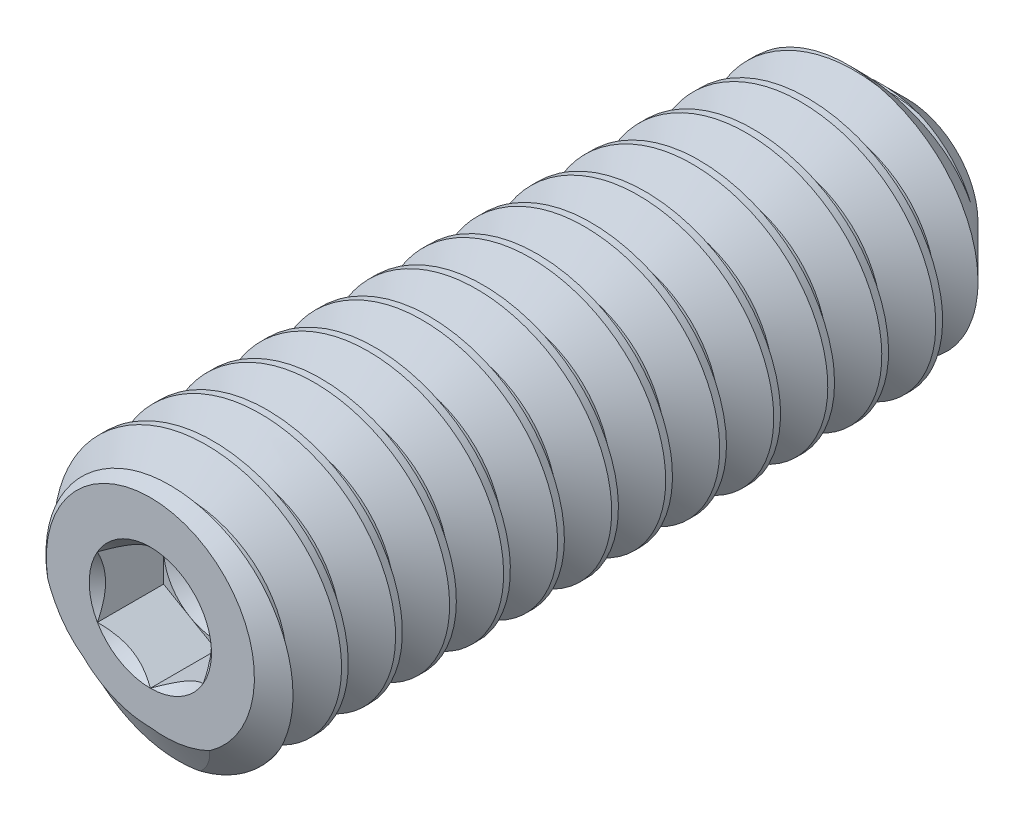
SolidWorks part; units mm, degrees
ref_plane "Front" through (0, 0, 0) normal (0, 0, 1) x (1, 0, 0)
ref_plane "Top" through (0, 0, 0) normal (0, 1, 0) x (1, 0, 0)
ref_plane "Right" through (0, 0, 0) normal (1, 0, 0) x (0, 0, -1)
sketch "Sketch22" plane through (0, 0, 0) normal (1, 0, 0) x (0, 0, -1)
  line L0 (-2.9952, 0) -> (-2.9952, 0.8738)
  line L1 (-2.9952, 0.8738) -> (-2.8422, 1.0922)
  line L2 (-2.8422, 1.0922) -> (2.8611, 1.0922)
  line L3 (2.8611, 1.0922) -> (3.3548, 0.5985)
  line L4 (3.3548, 0.5985) -> (2.9952, 0)
  line L5 (2.9952, 0) -> (-2.9952, 0)
  line L6 (2.9952, 0) -> (3.3548, 0) construction
  line L7 (3.3548, 0) -> (3.3548, 0.5985) construction
  line L8 (3.3548, -0.5985) -> (2.9952, 0) construction
  line L9 (-2.8422, -1.0922) -> (2.8611, -1.0922) construction
  line L10 (3.3548, -1.0922) -> (3.3548, 1.0922) construction
  line L11 (3.3548, 1.0922) -> (2.9012, 1.0922) construction
  point P11 (2.2209, -1.0922)
  point P15 (3.3548, 0)
  dimension "D3" = 35
  dimension "D5" = 118
  dimension "D6" = 45
  dimension "D7" = 1.7475
  dimension "D1" = 1.1339
revolve "Revolve1" add sketch "Sketch22" angle 360 about L6
ref_plane "Plane1" through (0, 0, -3.3548) normal (0, 0, 1) x (1, 0, 0)
sketch "Sketch27" plane through (0, 0, -3.3548) normal (0, 0, 1) x (1, 0, 0)
  circle A0 centre (0, 0) radius 1.0922 construction
  circle A1 centre (0, 0) radius 1.0922
sketch "Sketch23" plane through (0, 0, 2.9952) normal (0, 0, 1) x (1, 0, 0)
  line L1 (0, 0.5133) -> (-0.4445, 0.2566)
  line L2 (-0.4445, 0.2566) -> (-0.4445, -0.2566)
  line L3 (-0.4445, -0.2566) -> (0, -0.5133)
  line L4 (0, -0.5133) -> (0.4445, -0.2566)
  line L5 (0.4445, -0.2566) -> (0.4445, 0.2566)
  line L6 (0.4445, 0.2566) -> (0, 0.5133)
  circle A0 centre (0, 0) radius 0.4445 construction
extrude "Cut-Extrude10" cut sketch "Sketch23" against normal blind 0.5556
sketch "Sketch24" plane through (0, 0, 2.9952) normal (0, 0, 1) x (1, 0, 0)
  circle A0 centre (0, 0) radius 0.5133
extrude "Cut-Extrude11" cut sketch "Sketch24" against normal through all draft 45
sketch "Sketch26" plane through (0, 0, 2.4396) normal (0, 0, 1) x (1, 0, 0)
  circle A0 centre (0, 0) radius 0.4445 construction
  circle A1 centre (0, 0) radius 0.4445
extrude "Cut-Extrude12" cut sketch "Sketch26" against normal through all draft 60
sketch "Sketch31" plane through (0, 0, 0) normal (1, 0, 0) x (0, 0, -1)
  line L2 (2.9952, 0) -> (3.3548, -0.5985)
  line L3 (3.3548, 0.5985) -> (2.9952, 0)
ref_axis "Center Axis1" through (0, 0, -42.9554) along (0, 0, 1)
ref_plane "Contact Plane1" through (0, 0, -3.3548) normal (0, 0, 1) x (1, 0, 0)
ref_plane "Contact Plane2" through (0, 0, 2.9952) normal (0, 0, 1) x (1, 0, 0)
curve "Helix/Spiral1" pitch 0.4536 height 6.8036 radius 1.0922 centre (0, 0, -3.3548) axis (0, 0, 1) start towards (0, 1, 0)
sketch "Sketch32" plane through (0, 0, 0) normal (1, 0, 0) x (0, 0, -1)
  line L0 (3.3265, 1.1413) -> (3.78, 1.1413) construction
  line L1 (3.78, 1.1413) -> (3.5532, 0.7485) construction
  line L2 (3.5532, 0.7485) -> (3.3265, 1.1413) construction
  line L3 (3.3548, 1.0922) -> (2.9012, 1.0922) construction
  line L4 (3.5532, 0.7485) -> (3.5532, 0.7976) construction
  line L5 (3.5532, 1.1413) -> (3.5532, 1.0922) construction
  line L6 (3.5249, 0.7976) -> (3.5816, 0.7976)
  line L7 (3.3548, 1.0922) -> (3.7517, 1.0922) construction
  line L8 (3.3406, 1.1168) -> (3.7659, 1.1168)
  line L9 (3.3406, 1.1168) -> (3.5249, 0.7976)
  line L10 (3.5816, 0.7976) -> (3.7659, 1.1168)
  point P11 (3.5532, 0.7976)
  point P13 (3.5532, 1.0922)
  point P17 (3.5532, 1.1168)
  dimension "D1" = 0.0567
sweep "Cut-Sweep1" cut profiles "Sketch32" path "Helix/Spiral1"
equation "\"D7@Sketch22\"=\"Dia@Sketch22\"*.8"
equation "\"D3@Helix/Spiral1\"=\"Length@Sketch22\" + \"Pitch@Sketch22\"l1\""
equation "\"hex Depth@Cut-Extrude10\" = \"Hex@Sketch23\" * .625"
equation "\"D1@Sketch22\"=\"Pitch@Sketch22\"*2.5"
equation "\"D4@Helix/Spiral1\"=\"Pitch@Sketch22\""
equation "\"D1@Sketch32\"=\"Pitch@Sketch22\"*.125"
